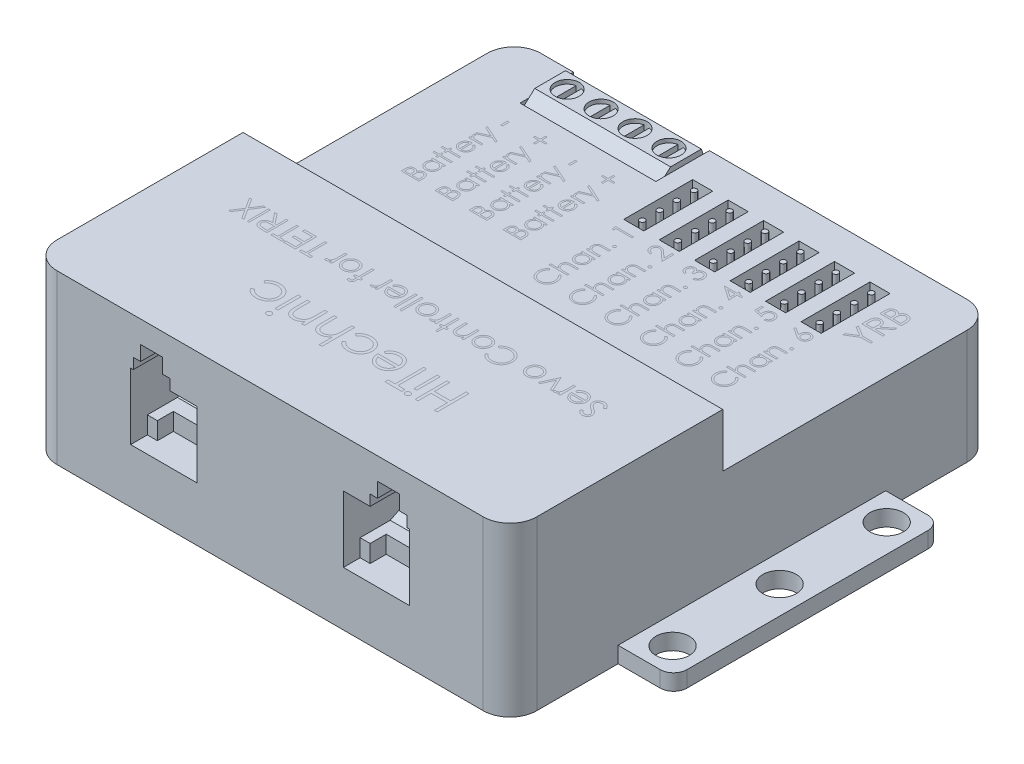
SolidWorks part; units mm, degrees
note: The reader was unsure of these and kept them because the rebuilt part matched: shared geometry of "Sketch3<3>", "Sketch3<4>", "Sketch7<3>".
other "Defeature"
material "ABS"
ref_plane "Front Plane" through (0, 0, 0) normal (0, 0, 1) x (1, 0, 0)
ref_plane "Top Plane" through (0, 0, 0) normal (0, 1, 0) x (1, 0, 0)
ref_plane "Right Plane" through (0, 0, 0) normal (1, 0, 0) x (0, 0, -1)
sketch "Sketch1" plane through (0, 0, 0) normal (1, 0, 0) x (0, 0, -1)
  line L0 (-36.15, 0) -> (36.15, 0)
  line L1 (36.15, 0) -> (36.15, 17.1)
  line L2 (36.15, 17.1) -> (-4.35, 17.1)
  line L3 (-4.35, 17.1) -> (-4.35, 25.1)
  line L4 (-4.35, 25.1) -> (-36.15, 25.1)
  line L5 (-36.15, 25.1) -> (-36.15, 0)
  point P7 (0, 0)
  dimension "D1" = 31.8
  dimension "D2" = 72.3
  dimension "D3" = 17.1
  dimension "D4" = 25.1
extrude "Boss-Extrude1" add sketch "Sketch1" along normal mid plane 71.7
sketch "Sketch2" plane through (0, 0, 36.15) normal (0, 0, 1) x (1, 0, 0)
  line L0 (14.95, 18) -> (14.95, 19.6)
  line L1 (10.95, 18) -> (20.85, 18)
  line L2 (10.95, 18) -> (10.95, 8.1)
  line L3 (10.95, 8.1) -> (20.85, 8.1)
  line L4 (20.85, 18) -> (20.85, 8.1)
  line L5 (10.95, 18) -> (20.85, 8.1) construction
  line L6 (10.95, 8.1) -> (20.85, 18) construction
  line L7 (14.95, 19.6) -> (16.05, 19.6)
  line L8 (20.45, 19.6) -> (20.45, 18)
  line L9 (16.05, 19.6) -> (16.05, 21.8)
  line L10 (16.05, 21.8) -> (19.35, 21.8)
  line L11 (19.35, 21.8) -> (19.35, 19.6)
  line L12 (19.35, 19.6) -> (20.45, 19.6)
  line L13 (35.85, 25.1) -> (35.85, 0) construction
  line L14 (35.85, 0) -> (-35.85, 0) construction
  point P0 (15.9, 13.05)
  dimension "D1" = 9.9
  dimension "D2" = 9.9
  dimension "D3" = 1.6
  dimension "D4" = 4
  dimension "D5" = 5.5
  dimension "D6" = 3.3
  dimension "D7" = 2.2
  dimension "D8" = 15
  dimension "D9" = 8.1
extrude "Cut-Extrude1" cut sketch "Sketch2" against normal blind 13 contours L12 L11 L10 L9 L7 L0 L1 L8 | L4 L1 L2 L3
sketch "Sketch3" plane through (20.85, 0, 0) normal (-1, 0, 0) x (0, 0, 1)
  line L0 (33.65, 8.1) -> (33.65, 10.7)
  line L1 (33.65, 10.7) -> (29.15, 10.7)
  line L2 (23.15, 15.1) -> (24.35, 15.1)
  line L3 (31.25, 10.7) -> (31.25, 8.1)
  line L4 (31.25, 8.1) -> (33.65, 8.1)
  line L5 (31.25, 8.1) -> (23.15, 8.1)
  line L6 (23.15, 8.1) -> (23.15, 15.1)
  line L7 (24.35, 15.1) -> (24.35, 13.1)
  line L8 (24.35, 13.1) -> (29.15, 10.7)
  line L9 (36.15, 18) -> (36.15, 8.1) construction
  line M3 (23.15, 18) -> (23.15, 8.1)
  line M4 (23.15, 8.1) -> (36.15, 8.1)
  dimension "D1" = 2.6
  dimension "D2" = 7
  dimension "D3" = 2
  dimension "D4" = 11.8
  dimension "D5" = 7
  dimension "D6" = 4.9
  dimension "D7" = 2.5
extrude "Boss-Extrude2" add sketch "Sketch3" along normal up to surface (9.9 mm away) contours L8 L7 L2 L3 L1 M3 M4 up to face at (10.95, 13.05, 29.65)
extrude "Boss-Extrude3" add sketch "Sketch3<3>" along normal blind 1.5 contours L1 L3 L0 M4
sketch "Sketch3<3>" plane through (20.85, 0, 0) normal (-1, 0, 0) x (0, 0, 1) same geometry as "Sketch3"
extrude "Boss-Extrude4" add sketch "Sketch3<4>" against normal blind 1.5 from surface at 9.9 contours L1 L3 L0 M4 starting at face at (10.95, 12.9889, 28.7722)
sketch "Sketch3<4>" plane through (20.85, 0, 0) normal (-1, 0, 0) x (0, 0, 1) same geometry as "Sketch3"
mirror "Mirror1" about plane through (0, 0, 0) normal (1, 0, 0) of "Cut-Extrude1", "Boss-Extrude2", "Boss-Extrude3", "Boss-Extrude4"
sketch "Sketch4" plane through (0, 17.1, 0) normal (0, 1, 0) x (1, 0, 0)
  line L0 (35.85, 36.15) -> (-35.85, 36.15) construction
  line L1 (26.95, 36.15) -> (6.65, 36.15)
  line L2 (26.95, 36.15) -> (26.95, 28.15)
  line L3 (26.95, 28.15) -> (6.65, 28.15)
  line L4 (6.65, 36.15) -> (6.65, 28.15)
  line L5 (35.85, 36.15) -> (35.85, -4.35) construction
  dimension "D1" = 20.3
  dimension "D2" = 8
  dimension "D3" = 8.9
extrude "Cut-Extrude2" cut sketch "Sketch4" against normal blind 9
sketch "Sketch5" plane through (6.65, 0, 0) normal (1, 0, 0) x (0, 0, -1)
  line L0 (36.15, 8.1) -> (36.15, 14.3)
  line L1 (36.15, 8.1) -> (36.15, 17.1) construction
  line L2 (36.15, 14.3) -> (34.95, 17.9)
  line L3 (34.95, 17.9) -> (30.35, 17.9)
  line L4 (30.35, 17.9) -> (28.15, 15.9)
  line L5 (28.15, 8.1) -> (28.15, 17.1) construction
  line L6 (28.15, 15.9) -> (28.15, 8.1)
  line L7 (36.15, 8.1) -> (28.15, 8.1) construction
  line L8 (28.15, 8.1) -> (36.15, 8.1)
  dimension "D1" = 6.2
  dimension "D2" = 9.8
  dimension "D3" = 2.2
  dimension "D4" = 1.2
  dimension "D5" = 2
extrude "Boss-Extrude5" add sketch "Sketch5" along normal up to surface (20.3 mm away) separate body up to face at (26.95, 12.6, -32.15)
sketch "Sketch6" plane through (0, 0, -36.15) normal (0, 0, -1) x (-1, 0, 0)
  line L0 (-16.8, 8.1) -> (-16.8, 14.3) construction
  line L1 (-26.95, 8.1) -> (-6.65, 8.1) construction
  line L2 (-26.95, 14.3) -> (-6.65, 14.3) construction
  line L3 (-24.4125, 11.2) -> (-19.3375, 11.2) construction
  line L4 (-19.3375, 11.2) -> (-14.2625, 11.2) construction
  line L5 (-14.2625, 11.2) -> (-9.1875, 11.2) construction
  line L6 (-24.4125, 11.2) -> (-29.4875, 11.2) construction
  line L7 (-9.1875, 11.2) -> (-4.1125, 11.2) construction
  line L8 (-26.95, 8.1) -> (-26.95, 17.1) construction
  circle A0 centre (-24.4125, 11.2) radius 1.75
  circle A1 centre (-19.3375, 11.2) radius 1.75
  circle A2 centre (-14.2625, 11.2) radius 1.75
  circle A3 centre (-9.1875, 11.2) radius 1.75
  point P14 (-16.8, 11.2)
  point P15 (-26.95, 11.2)
  dimension "D1" = 3.5
extrude "Cut-Extrude3" cut sketch "Sketch6" against normal blind 6
sketch "Sketch7" plane through (0, 17.9, 0) normal (0, 1, 0) x (1, 0, 0)
  line L0 (16.8, 34.95) -> (16.8, 30.35) construction
  line L1 (26.95, 34.95) -> (6.65, 34.95) construction
  line L2 (26.95, 30.35) -> (6.65, 30.35) construction
  line L3 (8.7875, 34.405) -> (8.7875, 30.895)
  line L4 (9.5875, 30.895) -> (9.5875, 34.405)
  line L5 (13.8625, 34.405) -> (13.8625, 30.895)
  line L6 (14.6625, 30.895) -> (14.6625, 34.405)
  line L7 (9.1875, 32.65) -> (14.2625, 32.65) construction
  line L8 (14.2625, 32.65) -> (19.3375, 32.65) construction
  line L9 (9.1875, 32.65) -> (4.1125, 32.65) construction
  line L10 (6.65, 34.95) -> (6.65, 30.35) construction
  line L11 (18.9375, 30.895) -> (18.9375, 34.405)
  line L12 (19.7375, 34.405) -> (19.7375, 30.895)
  line L13 (24.8125, 34.405) -> (24.8125, 30.895)
  line L14 (24.0125, 30.895) -> (24.0125, 34.405)
  circle A0 centre (9.1875, 32.65) radius 1.8
  circle A1 centre (14.2625, 32.65) radius 1.8
  circle A2 centre (19.3375, 32.65) radius 1.8
  circle A3 centre (24.4125, 32.65) radius 1.8
  point P10 (16.8, 32.65)
  point P11 (6.65, 32.65)
  point P24 (16.8, 32.65)
  dimension "D2" = 3.6
  dimension "D1" = 0.8
extrude "Cut-Extrude4" cut sketch "Sketch7" against normal blind 0.6 contours L4 A0 | L3 A0 | L5 A1 | L6 A1 | A2 L11 | A2 L12 | A3 L14 | A3 L13
extrude "Cut-Extrude5" cut sketch "Sketch7<3>" against normal blind 2 contours A3 L14 L13 | A2 L11 L12 | L6 A1 L5 | L4 A0 L3
sketch "Sketch7<3>" plane through (0, 17.9, 0) normal (0, 1, 0) x (1, 0, 0) same geometry as "Sketch7"
mirror "Mirror2" about plane through (0, 0, 0) normal (1, 0, 0) of "Cut-Extrude2"
mirror "Mirror3" about plane through (0, 0, 0) normal (1, 0, 0) of bodies 111
sketch "Sketch8" plane through (0, 17.1, 0) normal (0, 1, 0) x (1, 0, 0)
  line L0 (0, 0) -> (0, 36.15) construction
  line L1 (-4.15, 20.85) -> (-1.15, 20.85)
  line L2 (-4.15, 20.85) -> (-4.15, 31.15)
  line L3 (-4.15, 31.15) -> (-1.15, 31.15)
  line L4 (-1.15, 20.85) -> (-1.15, 31.15)
  line L5 (1.15, 20.85) -> (4.15, 20.85)
  line L6 (1.15, 20.85) -> (1.15, 31.15)
  line L7 (1.15, 31.15) -> (4.15, 31.15)
  line L8 (4.15, 20.85) -> (4.15, 31.15)
  line L9 (6.65, 36.15) -> (-6.65, 36.15) construction
  line L10 (2.65, 27.2875) -> (2.65, 29.8625) construction
  line L11 (2.65, 24.7125) -> (2.65, 27.2875) construction
  line L12 (2.65, 22.1375) -> (2.65, 24.7125) construction
  line L13 (2.65, 22.1375) -> (2.65, 19.5625) construction
  line L14 (2.65, 29.8625) -> (2.65, 32.4375) construction
  circle A0 centre (2.65, 22.1375) radius 0.4
  circle A1 centre (2.65, 24.7125) radius 0.4
  circle A2 centre (2.65, 27.2875) radius 0.4
  circle A3 centre (2.65, 29.8625) radius 0.4
  circle A4 centre (-2.65, 29.8625) radius 0.4
  circle A5 centre (-2.65, 27.2875) radius 0.4
  circle A6 centre (-2.65, 24.7125) radius 0.4
  circle A7 centre (-2.65, 22.1375) radius 0.4
  point P29 (2.65, 31.15)
  point P32 (2.65, 20.85)
  point P33 (2.65, 31.15)
  dimension "D5" = 0.8
  dimension "D1" = 10.3
  dimension "D2" = 3
  dimension "D3" = 2.3
  dimension "D4" = 5
extrude "Cut-Extrude6" cut sketch "Sketch8" against normal blind 4
sketch "Sketch9" plane through (0, 0, 0) normal (0, -1, 0) x (1, 0, 0)
  line L0 (35.85, 20) -> (44.15, 20)
  line L1 (35.85, 36.15) -> (35.85, -36.15) construction
  line L2 (44.15, 20) -> (44.15, -20)
  line L3 (44.15, -20) -> (35.85, -20)
  line L4 (35.85, 20) -> (35.85, -20)
  circle A0 centre (40, -16) radius 2.5
  circle A1 centre (40, 0) radius 2.5
  circle A2 centre (40, 16) radius 2.5
  point P5 (44.15, 0)
  point P14 (40, 20)
  dimension "D3" = 5
  dimension "D1" = 40
  dimension "D2" = 8.3
  dimension "D4" = 16
  dimension "D5" = 16
extrude "Boss-Extrude6" add sketch "Sketch9" against normal blind 2.4
fillet "Fillet1" radius 2 2 edges at (44.15, 1.2, 20) (44.15, 1.2, -20)
mirror "Mirror4" about plane through (0, 0, 0) normal (1, 0, 0) of "Fillet1", "Boss-Extrude6"
fillet "Fillet2" radius 4 4 edges at (-35.85, 12.55, 36.15) (35.85, 12.55, 36.15) (-35.85, 8.55, -36.15) (35.85, 8.55, -36.15)
sketch "Sketch10" plane through (0, 25.1, 0) normal (0, 1, 0) x (1, 0, 0)
  line L0 (-35.85, -12.35) -> (35.85, -12.35) construction
  line L1 (-35.85, -4.35) -> (-35.85, -32.15) construction
  line L2 (35.85, -20) -> (35.85, 20) construction
  line L3 (35.85, -4.35) -> (-35.85, -4.35) construction
  line L4 (35.85, -21.25) -> (-35.85, -21.25) construction
  line L5 (35.85, -4.35) -> (35.85, -32.15) construction
  text T0 "Servo Controller for TETRIX"
  text T1 "HiTechnic" font "Century Gothic" height in points 18
  dimension "D1" = 8
  dimension "D2" = 16.9
split line "Split Line1"
delete or keep bodies "Body-Delete1" type delete bodies bodies 111
sketch "Sketch12" plane through (0, 8.1, 0) normal (0, 1, 0) x (1, 0, 0)
  line L4 (26.95, 28.15) -> (26.95, 36.15)
  line L5 (26.95, 36.15) -> (6.65, 36.15)
  line L6 (6.65, 36.15) -> (6.65, 28.15)
  line L7 (6.65, 28.15) -> (26.95, 28.15)
  line L8 (26.95, 28.15) -> (26.95, 36.15)
  line L9 (26.95, 36.15) -> (6.65, 36.15)
  line L10 (6.65, 36.15) -> (6.65, 28.15)
  line L11 (6.65, 28.15) -> (26.95, 28.15)
  dimension "D1" = 0
extrude "Boss-Extrude7" add sketch "Sketch12" along normal up to surface (9 mm away) up to face at (2.65, 17.1, -26)
pattern_linear "LPattern1" count 3 spacing 10.6 along (1, 0, 0) of "Cut-Extrude6"
sketch "Sketch13" plane through (0, 17.1, 0) normal (0, 1, 0) x (1, 0, 0)
  line L0 (-24.4125, 30.85) -> (-24.4125, 10.15) construction
  line L1 (-19.3375, 30.85) -> (-19.3375, 10.15) construction
  line L2 (-14.2625, 30.85) -> (-14.2625, 10.15) construction
  line L3 (-9.1875, 30.85) -> (-9.1875, 10.15) construction
  line L4 (-1.15, 20.85) -> (-1.15, 6.15) construction
  line L6 (4.15, 20.85) -> (4.15, 6.15) construction
  line L8 (9.45, 20.85) -> (9.45, 6.15) construction
  line L10 (14.75, 20.85) -> (14.75, 6.15) construction
  line L12 (20.05, 20.85) -> (20.05, 6.15) construction
  line L14 (25.35, 20.85) -> (25.35, 6.15) construction
  line L16 (-26.95, 36.15) -> (-31.85, 36.15) construction
  line L17 (31.85, 36.15) -> (-6.65, 36.15) construction
  line L18 (30.35, 31.15) -> (30.35, 20.85) construction
  line L19 (25.35, 20.85) -> (25.35, 31.15) construction
  arc A0 (-24.8125, 30.895) -> (-24.0125, 30.895) centre (-24.4125, 32.65) ccw construction
  arc A1 (-19.7375, 30.895) -> (-18.9375, 30.895) centre (-19.3375, 32.65) ccw construction
  arc A2 (-14.6625, 30.895) -> (-13.8625, 30.895) centre (-14.2625, 32.65) ccw construction
  arc A3 (-9.5875, 30.895) -> (-8.7875, 30.895) centre (-9.1875, 32.65) ccw construction
  text T0 "Battery -" font "Century Gothic" height in points 10
  text T1 "Battery +" font "Century Gothic" height in points 10
  text T2 "Battery -" font "Century Gothic" height in points 10
  text T3 "Battery +" font "Century Gothic" height in points 10
  text T4 "Chan. 1" font "Century Gothic" height in points 10
  text T5 "Chan. 2" font "Century Gothic" height in points 10
  text T6 "Chan. 3" font "Century Gothic" height in points 10
  text T7 "Chan. 4" font "Century Gothic" height in points 10
  text T8 "Chan. 5" font "Century Gothic" height in points 10
  text T9 "Chan. 6" font "Century Gothic" height in points 10
  text T10 "YRB"
  dimension "D1" = 26
  dimension "D2" = 30
  dimension "D3" = 5
split line "Split Line2"
